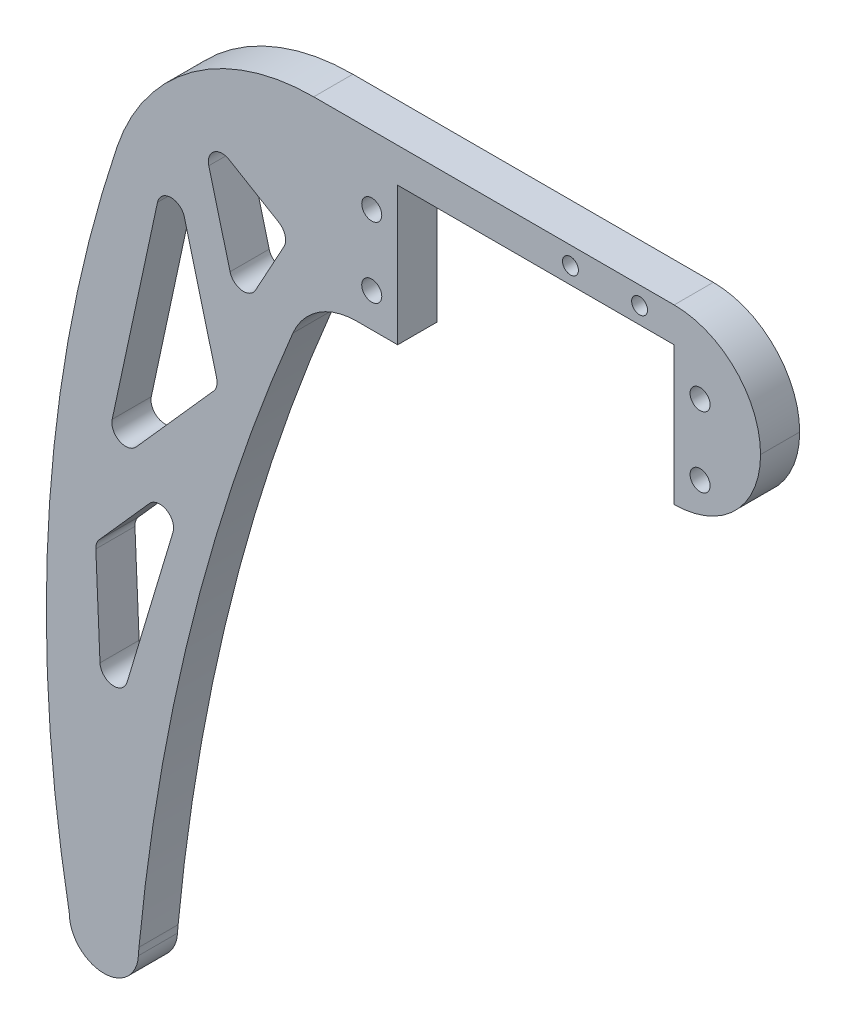
SolidWorks part; units mm, degrees
material "ABS"
ref_plane "Front" through (0, 0, 0) normal (0, 0, 1) x (1, 0, 0)
ref_plane "Top" through (0, 0, 0) normal (0, 1, 0) x (1, 0, 0)
ref_plane "Right" through (0, 0, 0) normal (1, 0, 0) x (0, 0, -1)
sketch "Esquisse1" plane through (0, 0, 0) normal (0, 0, 1) x (1, 0, 0)
  line L0 (-32.5, 12.5) -> (-52.5, 12.5)
  line L1 (-32.5, 12.5) -> (32.5, 12.5)
  line L3 (-32.5, -12.5) -> (32.5, -12.5)
  line L4 (32.5, 12.5) -> (32.5, -12.5)
  line L5 (-32.5, 12.5) -> (32.5, -12.5) construction
  line L6 (-32.5, -12.5) -> (32.5, 12.5) construction
  line L7 (-57.5, -107.5) -> (-67.5, -107.5) construction
  arc A3 (-32.5, -12.5) -> (-57.5, -107.5) centre (241.2075, -135.3178) ccw
  arc A4 (-57.5, -107.5) -> (-67.5, -107.5) centre (-62.5, -107.5) cw
  arc A5 (-52.5, 12.5) -> (-67.5, -107.5) centre (129.1682, -71.146) ccw
  point P0 (0, 0)
  point P12 (-62.5, -112.5)
  point P13 (-62.5, -107.5)
  dimension "D1" = 300
  dimension "D4" = 200
  dimension "D7" = 20
  dimension "D6" = 30
  dimension "D8" = 5
  dimension "D2" = 65
  dimension "D3" = 25
  dimension "D5" = 100
extrude "Boss.-Extru.1" add sketch "Esquisse1" along normal blind 5.66
sketch "Esquisse2" plane through (0, 0, 5.66) normal (0, 0, 1) x (1, 0, 0)
  line L0 (-32.5, 12.5) -> (-32.5, -12.5) construction
  line L1 (32.5, -12.5) -> (32.5, 12.5) construction
  line L2 (-32.5, -12.5) -> (32.5, -12.5) construction
  line L3 (-20, -12.5) -> (20, -12.5)
  line L4 (-20, -12.5) -> (-20, 7.5)
  line L5 (-20, 7.5) -> (20, 7.5)
  line L6 (20, -12.5) -> (20, 7.5)
  line L7 (-32.5, -12.5) -> (32.5, -12.5) construction
  dimension "D1" = 40
  dimension "D2" = 12.5
  dimension "D3" = 20
extrude "Enlèv. mat.-Extru.1" cut sketch "Esquisse2" against normal up to next
sketch "Esquisse3" plane through (0, 0, 5.66) normal (0, 0, 1) x (1, 0, 0)
  line L0 (-23.75, -7.58) -> (-20, -7.58) construction
  line L1 (-20, 7.5) -> (-20, -12.5) construction
  line L2 (23.75, -7.58) -> (20, -7.58) construction
  line L3 (20, -12.5) -> (20, 7.5) construction
  line L4 (-20, -2.5) -> (20, -2.5) construction
  circle A0 centre (-23.75, -7.58) radius 1.45
  circle A1 centre (23.75, -7.58) radius 1.45
  circle A2 centre (23.75, 2.58) radius 1.45
  circle A3 centre (-23.75, 2.58) radius 1.45
  dimension "D1" = 47.5
  dimension "D2" = 5.08
  dimension "D3" = 2.9
  dimension "D4" = 3.75
extrude "Enlèv. mat.-Extru.2" cut sketch "Esquisse3" against normal up to next
fillet "Congé2" radius 12.5 2 edges at (32.5, -12.5, 2.83) (32.5, 12.5, 2.83)
fillet "Congé3" radius 10 1 edges at (-32.5, -12.5, 2.83)
fillet "Congé4" radius 30 1 edges at (-52.5, 12.5, 2.83)
fillet "Congé5" radius 30 1 edges at (-57.5, -107.5, 2.83)
sketch "Esquisse4" plane through (0, 0, 5.66) normal (0, 0, 1) x (1, 0, 0)
  line L0 (-35.5305, -6.7417) -> (-42.9742, -20.3323)
  line L1 (-42.9742, -20.3323) -> (-48.5558, 0.9897)
  line L2 (-48.5558, 0.9897) -> (-35.5305, -6.7417)
  line L3 (-52.9829, -3.8169) -> (-45.9191, -30.8008)
  line L4 (-45.9191, -30.8008) -> (-62.9006, -49.9135)
  line L5 (-62.9006, -49.9135) -> (-52.9829, -3.8169)
  line L6 (-49.8982, -43.5599) -> (-63.7025, -59.0966)
  line L7 (-63.7025, -59.0966) -> (-62.553, -85.6965)
  line L8 (-62.553, -85.6965) -> (-49.8982, -43.5599)
  dimension "D1" = 5.5
  dimension "D2" = 5.5
extrude "Enlèv. mat.-Extru.3" cut sketch "Esquisse4" against normal up to next
fillet "Congé6" radius 2 9 edges at (-62.553, -85.6965, 2.83) (-63.7025, -59.0966, 2.83) (-49.8982, -43.5599, 2.83) (-45.9191, -30.8008, 2.83) (-52.9829, -3.8169, 2.83) (-62.9006, -49.9135, 2.83) (-42.9742, -20.3323, 2.83) (-35.5305, -6.7417, 2.83) (-48.5558, 0.9897, 2.83)
sketch "Esquisse5" plane through (0, 0, 5.66) normal (0, 0, 1) x (1, 0, 0)
  line L0 (20, 12.5) -> (-32.1455, 12.5) construction
  line L2 (20, -12.5) -> (20, 7.5) construction
  circle A0 centre (15, 9.91) radius 1.15
  circle A1 centre (5, 9.91) radius 1.15
  point P6 (0, 0)
  dimension "D1" = 2.59
  dimension "D2" = 10
  dimension "D3" = 5
  dimension "D4" = 2.3
extrude "Enlèv. mat.-Extru.4" cut sketch "Esquisse5" against normal up to next
